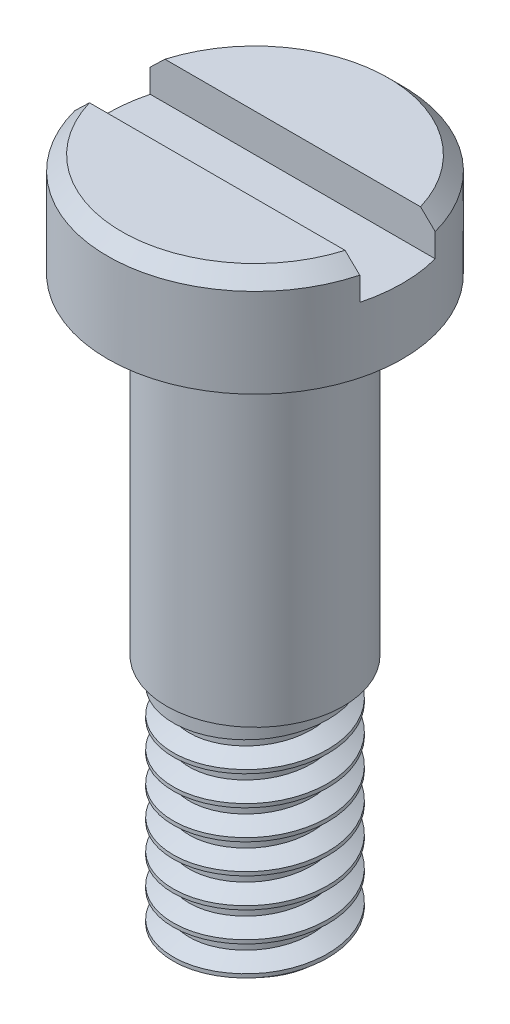
SolidWorks part; units mm, degrees
ref_plane "Front Plane" through (0, 0, 0) normal (0, 0, 1) x (1, 0, 0)
ref_plane "Top Plane" through (0, 0, 0) normal (0, 1, 0) x (1, 0, 0)
ref_plane "Right Plane" through (0, 0, 0) normal (1, 0, 0) x (0, 0, -1)
sketch "Sketch1" plane through (0, 0, 0) normal (0, 1, 0) x (1, 0, 0)
  circle A0 centre (0, 0) radius 2.3812
  dimension "D1" = 4.7625
extrude "Boss-Extrude1" add sketch "Sketch1" along normal blind 8.89
sketch "Sketch2" plane through (0, 8.89, 0) normal (0, 1, 0) x (1, 0, 0)
  circle A0 centre (0, 0) radius 3.9688
  dimension "D1" = 7.9375
extrude "Boss-Extrude2" add sketch "Sketch2" along normal blind 2.7781
chamfer "Chamfer1" distance 0.381 angle 45 1 edges at (0, 11.6681, 3.9688)
sketch "Sketch3" plane through (0, 0, 0) normal (0, -1, 0) x (1, 0, 0)
  circle A0 centre (0, 0) radius 2.0828
  dimension "D1" = 4.1656
extrude "Boss-Extrude3" add sketch "Sketch3" along normal blind 6.35
thread "Thread1" pitch 0.7937 method cut profile "Thread Profile1" start angle 0, offset 0, length 0, pitch 0.7937, diameter 4.1656
ref_plane "Plane1" through (-2.0828, 0, 0) normal (0, 0, 1) x (-1, 0, 0)
sketch "Thread Profile1" plane through (-2.0828, 0, 0) normal (0, 0, 1) x (-1, 0, 0)
  line L0 (0, 0) -> (0, 0.7937) construction
  line L11 (0, 0) -> (0, 0.6945)
  line L12 (0, 0.6945) -> (-0.4296, 0.4465)
  line L13 (-0.4296, 0.4465) -> (-0.4296, 0.248)
  line L15 (-0.4296, 0.248) -> (0, 0)
  line L17 (-0.4296, 0.3473) -> (0, 0.3473) construction
  point P2 (0, 0)
  dimension "Pitch" = 0.7937
  dimension "Profile_Angle" = 60
  dimension "Profile_Land" = 0.1984
  dimension "Profile_Height" = 0.4296
sketch "Sketch7" plane through (0, 11.6681, 0) normal (0, 1, 0) x (1, 0, 0)
  line L1 (-4.5452, 1.016) -> (4.8108, 1.016)
  line L2 (-4.5452, 1.016) -> (-4.5452, -1.016)
  line L3 (-4.5452, -1.016) -> (4.8108, -1.016)
  line L4 (4.8108, 1.016) -> (4.8108, -1.016)
  dimension "D1" = 2.032
  dimension "D2" = 1.016
extrude "Cut-Extrude1" cut sketch "Sketch7" against normal blind 1.016
